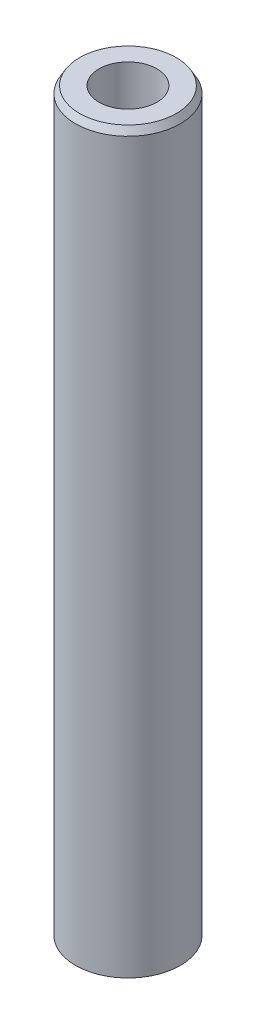
SolidWorks part; units mm, degrees
ref_plane "Front Plane" through (0, 0, 0) normal (0, 0, 1) x (1, 0, 0)
ref_plane "Top Plane" through (0, 0, 0) normal (0, 1, 0) x (1, 0, 0)
ref_plane "Right Plane" through (0, 0, 0) normal (1, 0, 0) x (0, 0, -1)
sketch "Sketch1" plane through (0, 0, 0) normal (0, 1, 0) x (1, 0, 0)
  circle A0 centre (0, 0) radius 42.5
  dimension "SHAFT_OD" = 85
extrude "Boss-Extrude1" add sketch "Sketch1" along normal blind 600
sketch "Sketch2" plane through (0, 0, 0) normal (0, 1, 0) x (1, 0, 0)
  circle A0 centre (0, 0) radius 23.5028
  dimension "BORE_D" = 47.0056
extrude "Cut-Extrude1" cut sketch "Sketch2" along normal through all
chamfer "Chamfer1" distance 5.6222 angle 30 2 edges at (0, 600, 42.5) (0, 0, 42.5) first distance on face at (0, 600, 42.5) first distance on face at (0, 0, 23.5028)
